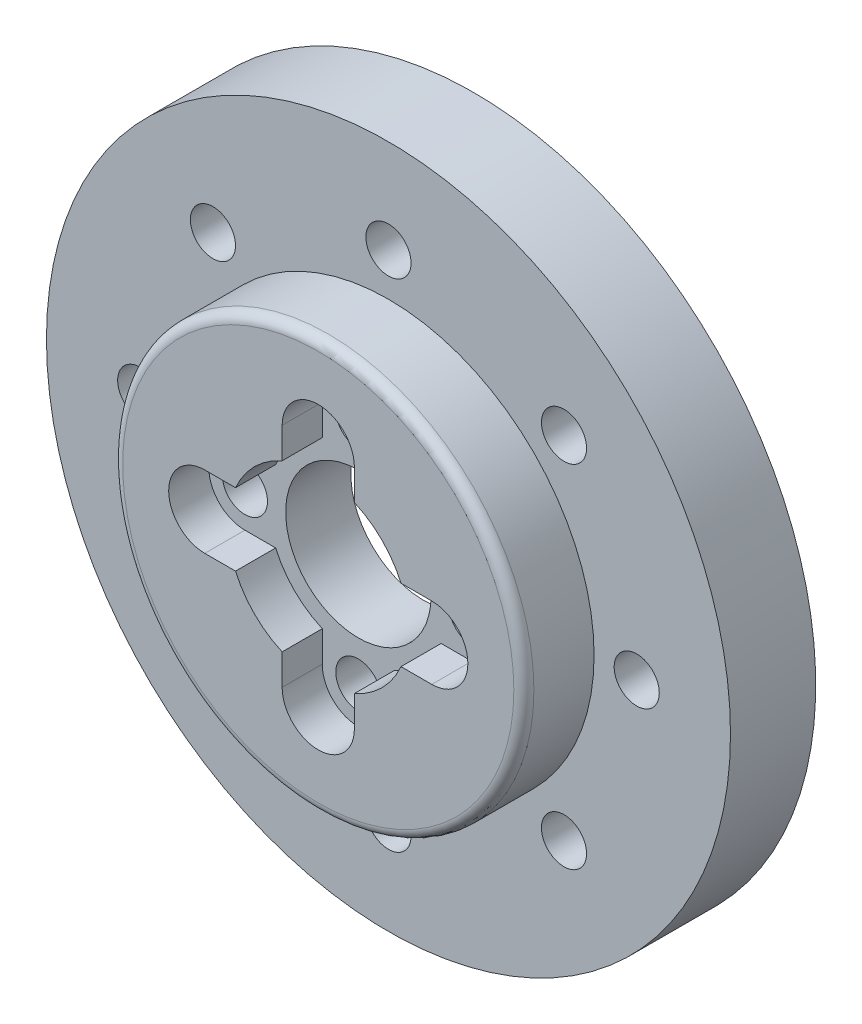
SolidWorks part; units mm, degrees
material "6061-T6 (SS)"
ref_plane "Front Plane" through (0, 0, 0) normal (0, 0, 1) x (1, 0, 0)
ref_plane "Top Plane" through (0, 0, 0) normal (0, 1, 0) x (1, 0, 0)
ref_plane "Right Plane" through (0, 0, 0) normal (1, 0, 0) x (0, 0, -1)
sketch "Sketch1" plane through (0, 0, 0) normal (0, 0, 1) x (1, 0, 0)
  circle A0 centre (0, 0) radius 34.1
  dimension "D1" = 68.2
extrude "Boss-Extrude1" add sketch "Sketch1" along normal mid plane 3.5
sketch "Sketch4" plane through (0, 0, 1.75) normal (0, 0, 1) x (1, 0, 0)
  circle A0 centre (0, 0) radius 28.5
  dimension "D1" = 57
extrude "Boss-Extrude2" add sketch "Sketch4" along normal blind 2
sketch "Sketch5" plane through (0, 0, -1.75) normal (0, 0, -1) x (-1, 0, 0)
  circle A0 centre (0, 0) radius 16.25
  circle A1 centre (0, 0) radius 34.1 construction
  circle A2 centre (0, 0) radius 34.1
  dimension "D1" = 32.5
extrude "Boss-Extrude3" add sketch "Sketch5" along normal blind 5
sketch "Sketch3" plane through (0, 0, 1.75) normal (0, 0, 1) x (1, 0, 0)
  circle A8 centre (0, 0) radius 11.3137 construction
  circle A9 centre (0, 11.3137) radius 2.25
  circle A11 centre (11.3137, 0) radius 2.25
  circle A13 centre (0, -11.3137) radius 2.25
  circle A15 centre (-11.3137, 0) radius 2.25
  point P21 (0, 0)
  dimension "D3" = 22.6274
  dimension "D4" = 4.5
  dimension "D5" = 4
extrude "Cut-Extrude2" cut sketch "Sketch3" against normal through all both and the other way through all
sketch "Sketch2" plane through (0, 0, 1.75) normal (0, 0, 1) x (1, 0, 0)
  circle A0 centre (0, 0) radius 7.25
  dimension "D1" = 14.5
extrude "Cut-Extrude1" cut sketch "Sketch2" along normal through all both and the other way through all
sketch "Sketch6" plane through (0, 0, 3.75) normal (0, 0, 1) x (1, 0, 0)
  circle A0 centre (0, 24.75) radius 2.25
  dimension "D1" = 4.5
  dimension "D2" = 24.75
extrude "Cut-Extrude3" cut sketch "Sketch6" against normal through all both and the other way through all
pattern_circular "CirPattern1" count 8 over 360 about axis through (0, 0, 1.75) along (0, 0, -1) of "Cut-Extrude3"
sketch "Sketch7" plane through (0, 0, 3.75) normal (0, 0, 1) x (1, 0, 0)
  circle A0 centre (0, 0) radius 20.5
  circle A5 centre (0, -11.3137) radius 2.25 construction
  circle A6 centre (11.3137, 0) radius 2.25 construction
  circle A7 centre (0, 11.3137) radius 2.25 construction
  circle A8 centre (-11.3137, 0) radius 2.25 construction
  circle A9 centre (0, 0) radius 7.25 construction
  circle A10 centre (0, -11.3137) radius 2.25
  circle A11 centre (11.3137, 0) radius 2.25
  circle A12 centre (0, 11.3137) radius 2.25
  circle A13 centre (-11.3137, 0) radius 2.25
  circle A14 centre (0, 0) radius 7.25
  dimension "D1" = 41
extrude "Boss-Extrude4" add sketch "Sketch7" along normal blind 5
sketch "Sketch8" plane through (0, 0, 1.75) normal (0, 0, 1) x (1, 0, 0)
  circle A0 centre (0, 0) radius 28.5 construction
  circle A1 centre (0, 0) radius 34.1
  circle A2 centre (0, 0) radius 34.1
  circle A3 centre (0, 0) radius 28.5
  dimension "D1" = 0
extrude "Boss-Extrude5" add sketch "Sketch8" along normal up to surface (2 mm away) up to face at (20.5, 0, 3.75)
sketch "Sketch10" plane through (0, 0, 3.75) normal (0, 0, 1) x (1, 0, 0)
  circle A0 centre (0, 0) radius 20.5 construction
  circle A1 centre (0, 0) radius 34.1
  circle A2 centre (0, 0) radius 34.1
  circle A3 centre (0, 0) radius 20.5
  dimension "D1" = 0
extrude "Cut-Extrude4" cut sketch "Sketch10" against normal blind 2
sketch "Sketch11" plane through (0, 0, 8.75) normal (0, 0, 1) x (1, 0, 0)
  line L0 (-11.3137, 3.6) -> (-8.2486, 3.6)
  line L1 (-3.6, 8.2486) -> (-3.6, 11.3137)
  line L2 (3.6, 11.3137) -> (3.6, 8.2486)
  line L3 (8.2486, 3.6) -> (11.3137, 3.6)
  line L4 (11.3137, -3.6) -> (8.2486, -3.6)
  line L5 (3.6, -8.2486) -> (3.6, -11.3137)
  line L6 (-3.6, -11.3137) -> (-3.6, -8.2486)
  line L7 (-8.2486, -3.6) -> (-11.3137, -3.6)
  circle A0 centre (-11.3137, 0) radius 2.25 construction
  circle A1 centre (0, -11.3137) radius 2.25 construction
  circle A2 centre (11.3137, 0) radius 2.25 construction
  circle A3 centre (0, 11.3137) radius 2.25 construction
  circle A4 centre (-11.3137, 0) radius 2.25 construction
  circle A5 centre (0, -11.3137) radius 2.25 construction
  circle A6 centre (11.3137, 0) radius 2.25 construction
  circle A7 centre (0, 11.3137) radius 2.25 construction
  arc A8 (-3.6, -11.3137) -> (3.6, -11.3137) centre (0, -11.3137) ccw
  arc A9 (11.3137, -3.6) -> (11.3137, 3.6) centre (11.3137, 0) ccw
  arc A10 (3.6, 11.3137) -> (-3.6, 11.3137) centre (0, 11.3137) ccw
  arc A11 (-11.3137, 3.6) -> (-11.3137, -3.6) centre (-11.3137, 0) ccw
  arc A12 (-8.2486, -3.6) -> (-3.6, -8.2486) centre (0, 0) ccw
  arc A13 (-3.6, 8.2486) -> (-8.2486, 3.6) centre (0, 0) ccw
  arc A14 (8.2486, 3.6) -> (3.6, 8.2486) centre (0, 0) ccw
  arc A15 (3.6, -8.2486) -> (8.2486, -3.6) centre (0, 0) ccw
  dimension "D1" = 7.2
  dimension "D2" = 18
extrude "Cut-Extrude5" cut sketch "Sketch11" against normal blind 4
sketch "Sketch12" plane through (0, 0, -6.75) normal (0, 0, -1) x (-1, 0, 0)
  circle A0 centre (0, 24.75) radius 4.6
  circle A1 centre (17.5009, 17.5009) radius 4.6
  circle A2 centre (24.75, 0) radius 4.6
  circle A3 centre (17.5009, -17.5009) radius 4.6
  circle A4 centre (0, -24.75) radius 4.6
  circle A5 centre (-17.5009, -17.5009) radius 4.6
  circle A6 centre (-24.75, 0) radius 4.6
  circle A7 centre (-17.5009, 17.5009) radius 4.6
  point P19 (0, 0)
  dimension "D1" = 9.2
  dimension "D2" = 8
extrude "Cut-Extrude6" cut sketch "Sketch12" against normal blind 3
fillet "Fillet2" radius 1 1 edges at (20.5, 0, 8.75)
